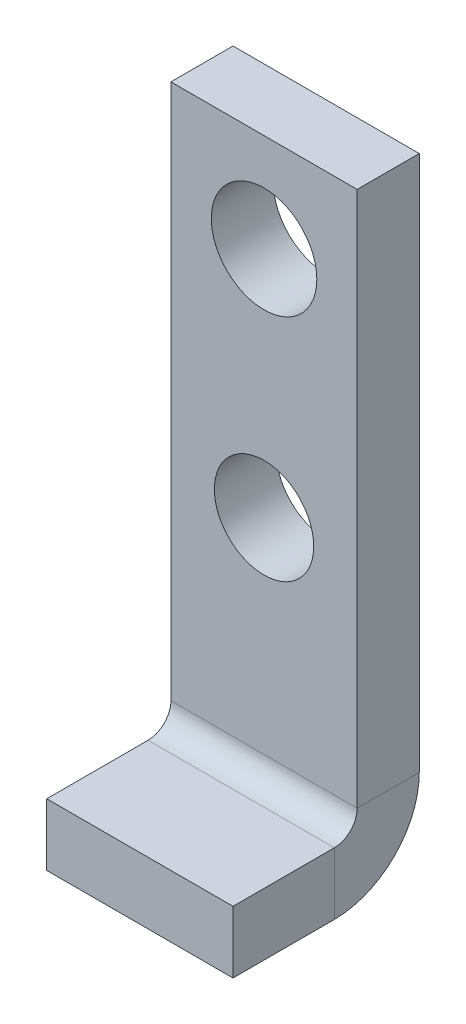
SolidWorks part; units mm, degrees
note: The reader was unsure of these and kept them because the rebuilt part matched: flange length of "Ребро-кромка1".
ref_plane "Спереди" through (0, 0, 0) normal (0, 0, 1) x (1, 0, 0)
ref_plane "Сверху" through (0, 0, 0) normal (0, 1, 0) x (1, 0, 0)
ref_plane "Справа" through (0, 0, 0) normal (1, 0, 0) x (0, 0, -1)
sketch "Эскиз1" plane through (0, 0, 0) normal (0, 0, 1) x (1, 0, 0)
  line L0 (0, -7.3403) -> (0, 10.6597) construction
  line L1 (-3, 10.6597) -> (3, 10.6597)
  line L2 (-3, 10.6597) -> (-3, -7.3403)
  line L3 (-3, -7.3403) -> (3, -7.3403)
  line L4 (3, 10.6597) -> (3, -7.3403)
  circle A0 centre (0, 0) radius 1.6
  circle A1 centre (0, 7.5) radius 1.7
  point P11 (0, 0)
  dimension "D1" = 7.5
  dimension "D2" = 3.4
  dimension "D3" = 3.2
  dimension "D4" = 18
  dimension "D5" = 6
base flange "Базовая кромка1" sketch "Эскиз1" thickness 2 reverse thickness direction no parameters "D1"=0.7366
edge flange "Ребро-кромка1" sketch "Эскиз9" flange angle 90 flange length 4 flange position material outside bend radius 0.7366 thickness 2 relief rectangular parameters "D6"=10
sketch "Эскиз9" plane through (0, -7.3403, 0) normal (0, -1, 0) x (1, 0, 0)
  line L0 (-3, 0) -> (3, 0) construction
  line L1 (-3, 0) -> (3, 0)
  line L2 (-3, 0) -> (-3, 4)
  line L3 (-3, 4) -> (3, 4)
  line L4 (3, 4) -> (3, 0)
bend "EdgeBend1" bend radius 0.7366 bend angle 90 parameters "D5"=1
sketch "Сгиб-Линии1" plane through (0, 0, 0) normal (0, 1, 0) x (1, 0, 0)
sketch "Граничная рамка1" plane through (0, 0, 0) normal (0, 1, 0) x (1, 0, 0)
sheet metal parameters "Листовой металл4" thickness 2 parameters "D1"=0.7366
flat pattern "Развертка4" [suppressed]
sketch "Сгиб-Линии2" plane through (0, 0, 0) normal (0, 1, 0) x (1, 0, 0)
sketch "Граничная рамка2" [suppressed] plane through (0, 0, 0) normal (0, 1, 0) x (1, 0, 0)
sheet metal parameters "Листовой металл5" thickness 2 parameters "D1"=0.7366
flat pattern "Развертка4" [suppressed]
sketch "Сгиб-Линии2" plane through (0, 0, 0) normal (0, 1, 0) x (1, 0, 0)
sketch "Граничная рамка2" [suppressed] plane through (0, 0, 0) normal (0, 1, 0) x (1, 0, 0)
bend of the flat pattern "Плоское состояние-<EdgeBend1>1"
